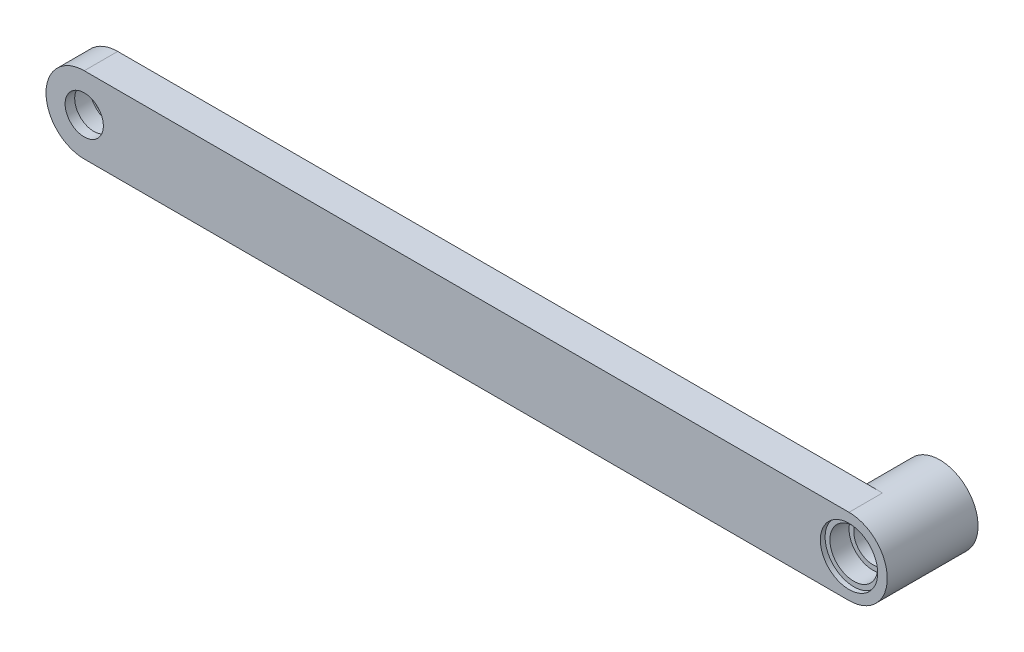
SolidWorks part; units mm, degrees
ref_plane "前视基准面" through (0, 0, 0) normal (0, 0, 1) x (1, 0, 0)
ref_plane "上视基准面" through (0, 0, 0) normal (0, 1, 0) x (1, 0, 0)
ref_plane "右视基准面" through (0, 0, 0) normal (1, 0, 0) x (0, 0, -1)
sketch "草图3" plane through (0, 0, 0) normal (0, 0, 1) x (1, 0, 0)
  line L1 (0, 4) -> (80, 4)
  line L2 (0, -4) -> (80, -4)
  arc A0 (0, 4) -> (0, -4) centre (0, 0) ccw
  arc A1 (80, -4) -> (80, 4) centre (80, 0) ccw
  dimension "D2" = 8
  dimension "D3" = 8
  dimension "D1" = 80
extrude "凸台-拉伸1" add sketch "草图3" along normal blind 3.5
sketch "草图4" plane through (0, 0, 0) normal (0, 0, -1) x (-1, 0, 0)
  circle A0 centre (0, 0) radius 3
  circle A1 centre (0, 0) radius 2.5
  circle A2 centre (0, 0) radius 2
  dimension "D1" = 6
  dimension "D2" = 5
  dimension "D3" = 4
extrude "切除-拉伸1" cut sketch "草图4" against normal through all contours A2 region at (0, 0, 0)
extrude "切除-拉伸2" cut sketch "草图4<3>" against normal blind 2.5 contours A1 A2 region at (2.4293, 0, 0)
sketch "草图4<3>" plane through (0, 0, 0) normal (0, 0, -1) x (-1, 0, 0) same geometry as "草图4"
extrude "切除-拉伸4" cut sketch "草图4<5>" against normal blind 0.5 contours A0 A1 region at (2.9151, 0, 0)
sketch "草图4<5>" plane through (0, 0, 0) normal (0, 0, -1) x (-1, 0, 0) same geometry as "草图4"
sketch "草图5" plane through (0, 0, 0) normal (0, 0, -1) x (-1, 0, 0)
  circle A0 centre (-80, 0) radius 4
extrude "凸台-拉伸2" add sketch "草图5" along normal blind 6
sketch "草图6" plane through (0, 0, -6) normal (0, 0, -1) x (-1, 0, 0)
  circle A0 centre (-80, 0) radius 3
  circle A1 centre (-80, 0) radius 2.5
  circle A2 centre (-80, 0) radius 2
  dimension "D1" = 6
  dimension "D2" = 5
  dimension "D3" = 4
extrude "切除-拉伸5" cut sketch "草图6" against normal through all contours A2 region at (80, 0, -6)
extrude "切除-拉伸6" cut sketch "草图6<3>" against normal blind 2.5 contours A1 A2 region at (82.4293, 0, -6)
sketch "草图6<3>" plane through (0, 0, -6) normal (0, 0, -1) x (-1, 0, 0) same geometry as "草图6"
extrude "切除-拉伸7" cut sketch "草图6<4>" against normal blind 0.5 contours A0 A1 region at (82.9151, 0, -6)
sketch "草图6<4>" plane through (0, 0, -6) normal (0, 0, -1) x (-1, 0, 0) same geometry as "草图6"
sketch "草图7" plane through (0, 0, 3.5) normal (0, 0, 1) x (1, 0, 0)
  circle A0 centre (80, 0) radius 3
  circle A1 centre (80, 0) radius 2.5
  dimension "D1" = 5
  dimension "D2" = 6
extrude "切除-拉伸8" cut sketch "草图7" against normal blind 2.5 contours A1
extrude "切除-拉伸9" cut sketch "草图7<3>" against normal blind 0.5
sketch "草图7<3>" plane through (0, 0, 3.5) normal (0, 0, 1) x (1, 0, 0) same geometry as "草图7"
